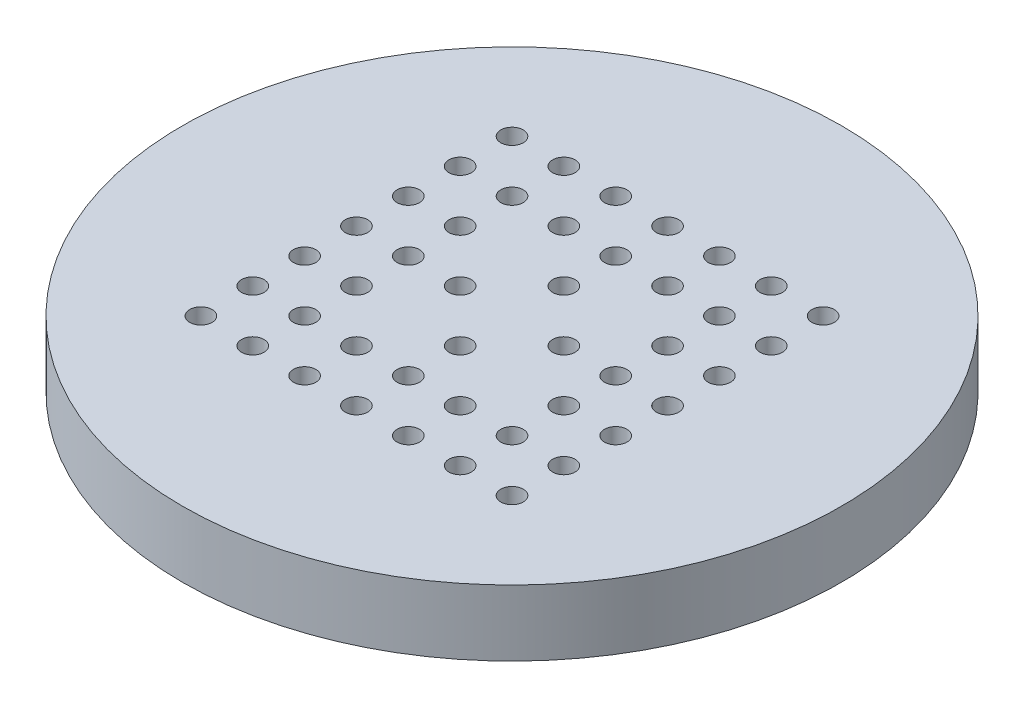
SolidWorks part; units mm, degrees
ref_plane "Front Plane" through (0, 0, 0) normal (0, 0, 1) x (1, 0, 0)
ref_plane "Top Plane" through (0, 0, 0) normal (0, 1, 0) x (1, 0, 0)
ref_plane "Right Plane" through (0, 0, 0) normal (1, 0, 0) x (0, 0, -1)
ref_axis "Axial" through (0, -55, 0) along (0, 1, 0)
ref_plane "Bottom Plane" through (0, -3.81, 0) normal (0, 1, 0) x (1, 0, 0)
sketch "Sketch1" plane through (0, 0, 0) normal (0, 1, 0) x (1, 0, 0)
  circle A0 centre (0, 0) radius 19.05
  dimension "D1" = 38.1
extrude "Billet" add sketch "Sketch1" against normal blind 3.81
sketch "Sketch2" plane through (0, 0, 0) normal (0, 1, 0) x (1, 0, 0)
  line L0 (0, 18.6449) -> (0, -20.0163) construction
  line L1 (-17.698, 0) -> (15.8694, 0) construction
  circle A0 centre (8.9916, 8.9916) radius 0.6477
  dimension "D1" = 1.2954
  dimension "D2" = 8.9916
  dimension "D3" = 8.9916
extrude "First Lox Hole" cut sketch "Sketch2" against normal through all and the other way through all contours A0
chamfer "Braising Chamfer" distance 0.254 angle 45 1 edges at (8.9916, -3.81, -8.3439)
pattern_linear "Lox Hole Pattern" count 7 spacing 2.9972 along (-1, 0, 0) count 7 spacing 2.9972 along (0, 0, 1) skipping (2, 2), (2, 4), (3, 3), (4, 2), (4, 4) of "First Lox Hole", "Braising Chamfer"
sketch "Sketch3" plane through (0, -3.81, 0) normal (0, 1, 0) x (-1, 0, 0)
  line L0 (0, 21.0611) -> (0, -20.7325) construction
  line L1 (-20.4368, 0) -> (21.7511, 0) construction
  circle A3 centre (0, 15.24) radius 0.7937
  circle A4 centre (0, -15.24) radius 0.7937
  dimension "D4" = 15.24
  dimension "D3" = 1.5875
extrude "Dowel Hole" cut sketch "Sketch3" along normal blind 1.5875
